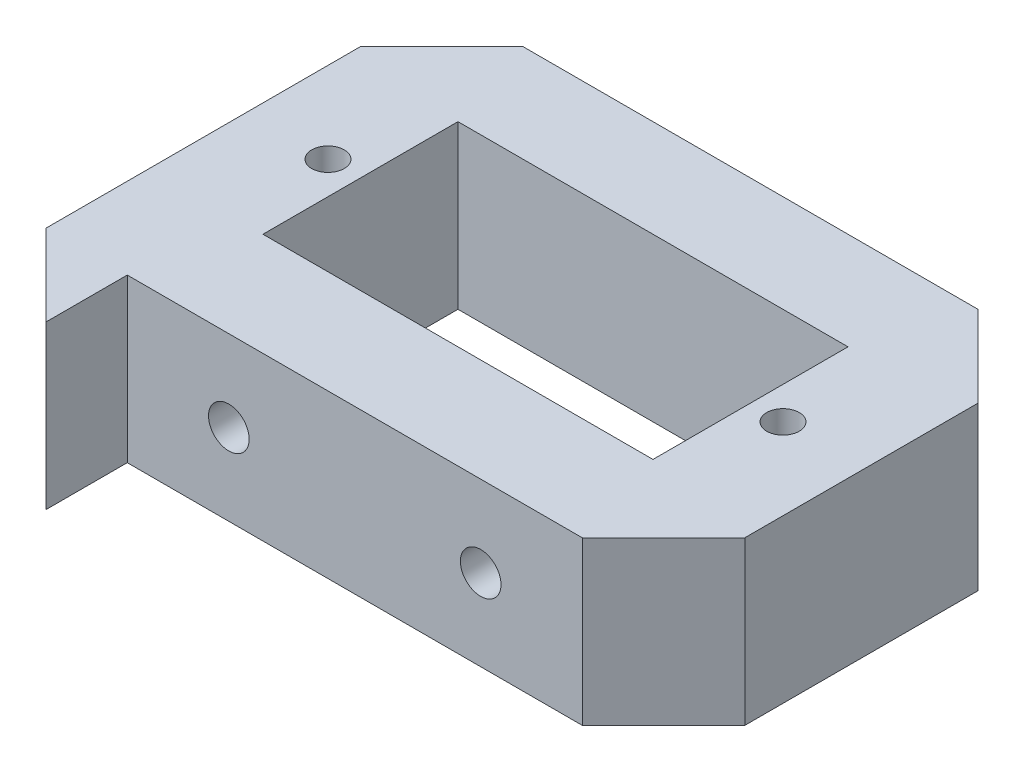
SolidWorks part; units mm, degrees
ref_plane "Front Plane" through (0, 0, 0) normal (0, 0, 1) x (1, 0, 0)
ref_plane "Top Plane" through (0, 0, 0) normal (0, 1, 0) x (1, 0, 0)
ref_plane "Right Plane" through (0, 0, 0) normal (1, 0, 0) x (0, 0, -1)
sketch "Sketch1" plane through (0, 0, 0) normal (0, 1, 0) x (1, 0, 0)
  line L0 (-18.9623, -7.5575) -> (19.0377, -7.5575)
  line L1 (-11.9623, 10.7925) -> (12.0377, 10.7925)
  line L2 (19.0377, -7.5575) -> (18.9349, -7.457)
  line L3 (12.0377, -1.2075) -> (-11.9623, -1.2075)
  line L4 (-18.9623, 16.7925) -> (19.0377, 16.7925)
  line L5 (19.0377, 4.7925) -> (19.0377, 16.7925)
  line L6 (16.0377, 4.7925) -> (12.0377, 4.7925) construction
  line L7 (-15.9623, 4.7925) -> (-11.9623, 4.7925) construction
  line L8 (-11.9623, 4.7925) -> (-11.9623, -1.2075)
  line L9 (-11.9623, -1.2075) -> (-11.9623, 10.7925)
  line L10 (12.0377, -1.2075) -> (12.0377, 10.7925)
  line L17 (-18.9623, 4.7925) -> (-18.9623, 16.7925)
  line L18 (-18.9623, 16.7925) -> (-18.9623, 4.7925)
  line L19 (-18.9623, -7.5575) -> (-18.9623, 4.7925)
  line L20 (19.0377, 4.7925) -> (19.0377, -7.5575)
  line L21 (19.0377, -7.5575) -> (19.0377, 4.7925)
  circle A0 centre (-13.9623, 4.7925) radius 1
  circle A1 centre (14.0377, 4.7925) radius 1
  dimension "D11" = 2
  dimension "D12" = 2
  dimension "D3" = 4
  dimension "D4" = 4
extrude "Boss-Extrude2" add sketch "Sketch1" along normal blind 10 contours L20 L5 L4 L17 L19 L0 A1 A0 L10 L3 L8 L9 L1 region at (-18.5109, 0, 1.3825)
chamfer "Chamfer1" distance 5 angle 45 4 edges at (-18.9623, 5, -16.7925) (-18.9623, 5, 7.5575) (19.0377, 5, -16.7925) (19.0377, 5, 7.5575)
sketch "Sketch3" plane through (0, 0, 7.5575) normal (0, 0, 1) x (1, 0, 0)
  line L0 (-13.9623, 5) -> (-7.7123, 5) construction
  line L1 (-13.9623, 10) -> (-13.9623, 0) construction
  line L2 (14.0377, 5) -> (7.7877, 5) construction
  line L3 (14.0377, 0) -> (14.0377, 10) construction
  circle A0 centre (-7.7123, 5) radius 1.25
  circle A1 centre (7.7877, 5) radius 1.25
extrude "Cut-Extrude1" cut sketch "Sketch3" against normal blind 12
sketch "Sketch4" plane through (0, 10, 0) normal (0, 1, 0) x (1, 0, 0)
  line L0 (-13.9623, -7.5575) -> (-13.9623, -12.5575) construction
  line L1 (-13.9623, -7.5575) -> (-13.9623, -12.5575)
  line L2 (-18.9623, -2.5575) -> (-18.9623, -12.5575)
  line L3 (-18.9623, -12.5575) -> (-13.9623, -12.5575)
  line L4 (-13.9623, -7.5575) -> (-13.9623, -0.9834)
  line L5 (-13.9623, -0.9834) -> (-18.9623, -2.5575)
  dimension "D1" = 5
extrude "Boss-Extrude3" add sketch "Sketch4" against normal blind 10
chamfer "Chamfer2" distance 5 angle 45 1 edges at (-18.9623, 5, 12.5575)
